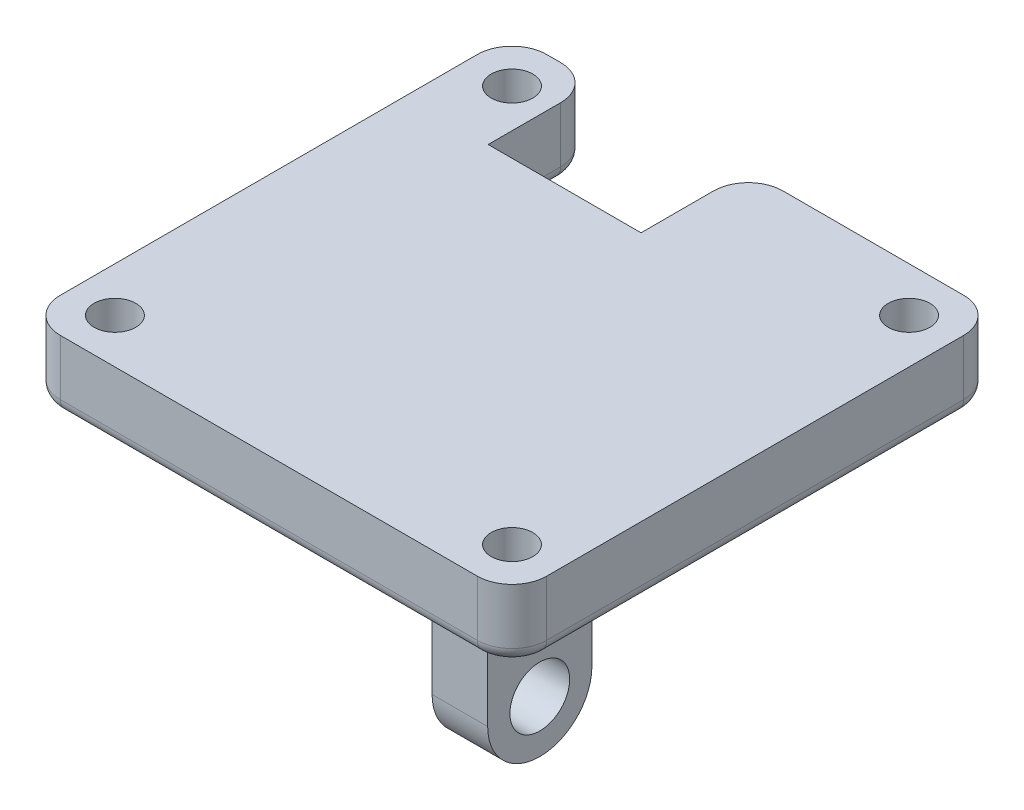
SolidWorks part; units mm, degrees
material "ABS"
ref_plane "Front" through (0, 0, 0) normal (0, 0, 1) x (1, 0, 0)
ref_plane "Top" through (0, 0, 0) normal (0, 1, 0) x (1, 0, 0)
ref_plane "Right" through (0, 0, 0) normal (1, 0, 0) x (0, 0, -1)
sketch "草图2" plane through (0, 0, 0) normal (0, 1, 0) x (1, 0, 0)
  line L0 (-15.785, 15.785) -> (-15.785, -15.785) construction
  line L1 (-17.5, -17.5) -> (17.5, -17.5)
  line L2 (-17.5, -17.5) -> (-17.5, 17.5)
  line L3 (-17.5, 17.5) -> (17.5, 17.5)
  line L4 (17.5, -17.5) -> (17.5, 17.5)
  line L5 (-17.5, -17.5) -> (17.5, 17.5) construction
  line L6 (-17.5, 17.5) -> (17.5, -17.5) construction
  line L7 (-15.785, -15.785) -> (15.785, -15.785) construction
  line L8 (15.785, -15.785) -> (15.785, 15.785) construction
  line L9 (15.785, 15.785) -> (-15.785, 15.785) construction
  point P0 (0, 0)
  dimension "D1" = 35
  dimension "D2" = 35
  dimension "D3" = 31.57
extrude "凸台-拉伸1" add sketch "草图2" along normal blind 5
sketch "草图3" plane through (0, 5, 0) normal (0, 1, 0) x (1, 0, 0)
  line L0 (-17.5, 17.5) -> (17.5, -17.5) construction
  line L1 (17.5, 17.5) -> (-17.5, -17.5) construction
  line L2 (-15.785, 15.785) -> (-15.785, -15.785) construction
  line L3 (-15.785, -15.785) -> (15.785, -15.785) construction
  line L4 (15.785, -15.785) -> (15.785, 15.785) construction
  line L5 (15.785, 15.785) -> (-15.785, 15.785) construction
  line L6 (-23.1151, 0) -> (31.4781, 0) construction
  line L7 (0, 0) -> (0, -12.6467) construction
  line L8 (17.5, 17.5) -> (-17.5, 17.5) construction
  line L9 (-11.5, 17.5) -> (-0.5, 17.5)
  line L10 (-11.5, 17.5) -> (-11.5, 9.785)
  line L11 (-11.5, 9.785) -> (-0.5, 9.785)
  line L12 (-0.5, 17.5) -> (-0.5, 9.785)
  line L13 (-17.5, 17.5) -> (-17.5, -17.5) construction
  circle A0 centre (-14.285, 14.285) radius 1.5
  circle A1 centre (-14.285, -14.285) radius 1.5
  circle A2 centre (14.285, -14.285) radius 1.5
  circle A3 centre (14.285, 14.285) radius 1.5
  dimension "D2" = 3
  dimension "D3" = 1.5
  dimension "D1" = 31.57
  dimension "D4" = 17
  dimension "D5" = 11
  dimension "D6" = 6
extrude "切除-拉伸1" cut sketch "草图3" against normal through all
sketch "草图4" plane through (0, 0, 0) normal (0, -1, 0) x (1, 0, 0)
  line L1 (-2.5, -4) -> (2.5, -4)
  line L2 (-2.5, -4) -> (-2.5, 4)
  line L3 (-2.5, 4) -> (2.5, 4)
  line L4 (2.5, -4) -> (2.5, 4)
  line L5 (-2.5, -4) -> (2.5, 4) construction
  line L6 (-2.5, 4) -> (2.5, -4) construction
  point P0 (0, 0)
  dimension "D1" = 5
  dimension "D2" = 8
extrude "凸台-拉伸2" add sketch "草图4" along normal blind 1.5
sketch "草图5" plane through (0, -1.5, 0) normal (0, -1, 0) x (1, 0, 0)
  line L1 (-2, -3.75) -> (2, -3.75)
  line L2 (-2, -3.75) -> (-2, 3.75)
  line L3 (-2, 3.75) -> (2, 3.75)
  line L4 (2, -3.75) -> (2, 3.75)
  line L5 (-2, -3.75) -> (2, 3.75) construction
  line L6 (-2, 3.75) -> (2, -3.75) construction
  point P0 (0, 0)
  dimension "D1" = 4
  dimension "D2" = 7.5
extrude "凸台-拉伸3" add sketch "草图5" along normal blind 20
fillet "圆角1" radius 3.75 2 edges at (0, -21.5, -3.75) (0, -21.5, 3.75)
sketch "草图6" plane through (-2, 0, 0) normal (-1, 0, 0) x (0, 0, 1)
  line L0 (-3.75, -17.75) -> (3.75, -17.75) construction
  circle A0 centre (0, -17.75) radius 2.15
  dimension "D1" = 4.3
extrude "切除-拉伸2" cut sketch "草图6" against normal blind 8
fillet "圆角2" radius 2.5 4 edges at (17.5, 2.5, -17.5) (17.5, 2.5, 17.5) (-17.5, 2.5, 17.5) (-17.5, 2.5, -17.5)
fillet "圆角3" radius 2.5 2 edges at (-0.5, 2.5, -17.5) (-11.5, 2.5, -17.5)
fillet "圆角4" radius 1 14 edges at (-11.5, 0, -12.3925) (-12.2322, 0, -16.7678) (-0.5, 0, -12.3925) (0.2322, 0, -16.7678) (8.5, 0, -17.5) (16.7678, 0, -16.7678) (17.5, 0, 0) (16.7678, 0, 16.7678) (0, 0, 17.5) (-16.7678, 0, 16.7678) (-17.5, 0, 0) (-16.7678, 0, -16.7678) (-6, 0, -9.785) (-14.5, 0, -17.5)
fillet "圆角5" radius 1 4 edges at (0, 0, 4) (2.5, 0, 0) (0, 0, -4) (-2.5, 0, 0)
fillet "圆角6" radius 1 4 edges at (0, -1.5, -4) (-2.5, -1.5, 0) (0, -1.5, 4) (2.5, -1.5, 0)
